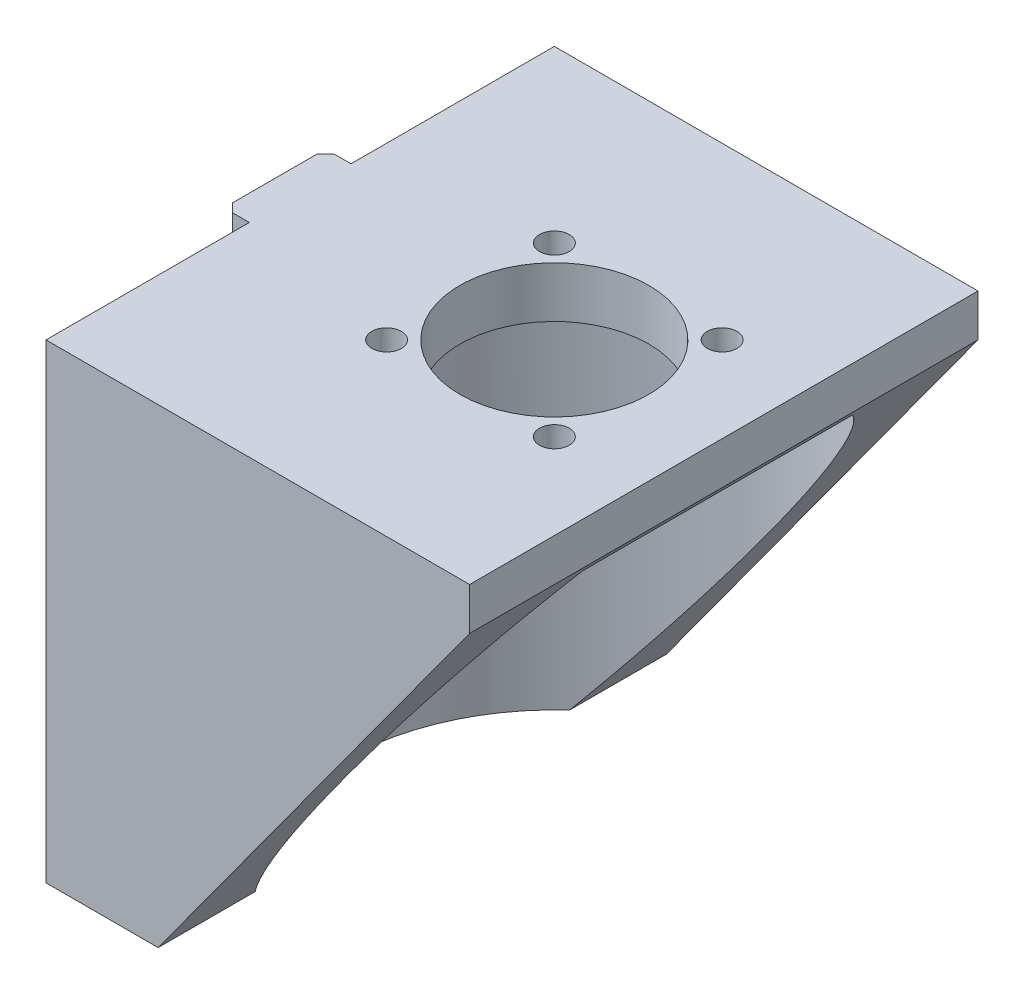
SolidWorks part; units mm, degrees
ref_plane "Płaszczyzna przednia" through (0, 0, 0) normal (0, 0, 1) x (1, 0, 0)
ref_plane "Płaszczyzna górna" through (0, 0, 0) normal (0, 1, 0) x (1, 0, 0)
ref_plane "Płaszczyzna prawa" through (0, 0, 0) normal (1, 0, 0) x (0, 0, -1)
sketch "Sketch1" plane through (0, 0, 0) normal (0, 0, 1) x (1, 0, 0)
  line L0 (0, 0) -> (13.235, 0)
  line L1 (13.235, 0) -> (50, 50.5)
  line L2 (50, 50.5) -> (50, 55.5)
  line L3 (50, 55.5) -> (0, 55.5)
  line L4 (0, 55.5) -> (0, 0)
  dimension "D1" = 55.5
  dimension "D2" = 50
  dimension "D3" = 5
extrude "Boss-Extrude1" add sketch "Sketch1" along normal blind 60
sketch "Sketch2" plane through (0, 0, 0) normal (0, 1, 0) x (1, 0, 0)
  line L0 (0, -60) -> (0, 0) construction
  line L5 (30, -30) -> (20.1005, -20.1005) construction
  line L7 (50, 0) -> (0, 0) construction
  line L9 (30, -30) -> (16, -30) construction
  circle A0 centre (30, -30) radius 11.15
  circle A5 centre (30, -30) radius 14 construction
  circle A6 centre (20.1005, -20.1005) radius 1.75
  circle A7 centre (39.8995, -20.1005) radius 1.75
  circle A8 centre (39.8995, -39.8995) radius 1.75
  circle A9 centre (20.1005, -39.8995) radius 1.75
  point P19 (30, -30)
  dimension "D1" = 45
  dimension "D6" = 22.3
  dimension "D7" = 28
  dimension "D2" = 3.5
  dimension "D3" = 4
  dimension "D4" = 30
  dimension "D5" = 30
extrude "Cut-Extrude2" cut sketch "Sketch2" along normal through all both and the other way through all
sketch "Sketch3" plane through (0, 0, 0) normal (0, 1, 0) x (1, 0, 0)
  circle A0 centre (30, -30) radius 25
  dimension "D1" = 50
extrude "Cut-Extrude4" cut sketch "Sketch3" along normal blind 49.5 contours A0
sketch "Sketch4" plane through (0, 0, 0) normal (1, 0, 0) x (0, 0, -1)
  line L0 (-48.5454, 0) -> (-11.4546, 0) construction
  line L1 (-60, 0) -> (-60, 50.5) construction
  circle A0 centre (-30, 12) radius 4.1
  circle A2 centre (-30, 40) radius 4.1
  point P4 (0, 0)
  point P5 (0, 0)
  dimension "D1" = 8.2
  dimension "D2" = 12
  dimension "D3" = 28
  dimension "D4" = 30
extrude "Cut-Extrude5" cut sketch "Sketch4" along normal through all both and the other way through all
sketch "Sketch5" plane through (0, 0, 0) normal (1, 0, 0) x (0, 0, -1)
  circle A0 centre (-30, 12) radius 6.5
  circle A1 centre (-30, 40) radius 6.5
  dimension "D1" = 13
  dimension "D2" = 13
extrude "Cut-Extrude6" cut sketch "Sketch5" against normal blind 47 from surface starting at face at (50, 53, 30)
sketch "Sketch6" plane through (0, 0, 0) normal (1, 0, 0) x (0, 0, -1)
  line L0 (-60, 55.5) -> (0, 55.5) construction
  line L1 (-24, 55.5) -> (-36, 55.5)
  line L2 (-24, 55.5) -> (-24, 0)
  line L3 (-24, 0) -> (-36, 0)
  line L4 (-36, 55.5) -> (-36, 0)
  line L5 (-60, 0) -> (0, 0) construction
  line L6 (0, 55.5) -> (0, 0) construction
  circle A0 centre (-30, 40) radius 4.1
  circle A1 centre (-30, 12) radius 4.1
  dimension "D1" = 24
  dimension "D2" = 12
extrude "Boss-Extrude2" add sketch "Sketch6" against normal blind 3
chamfer "Chamfer1" distance 1 angle 45 2 edges at (-3, 27.75, 24) (-3, 27.75, 36)
